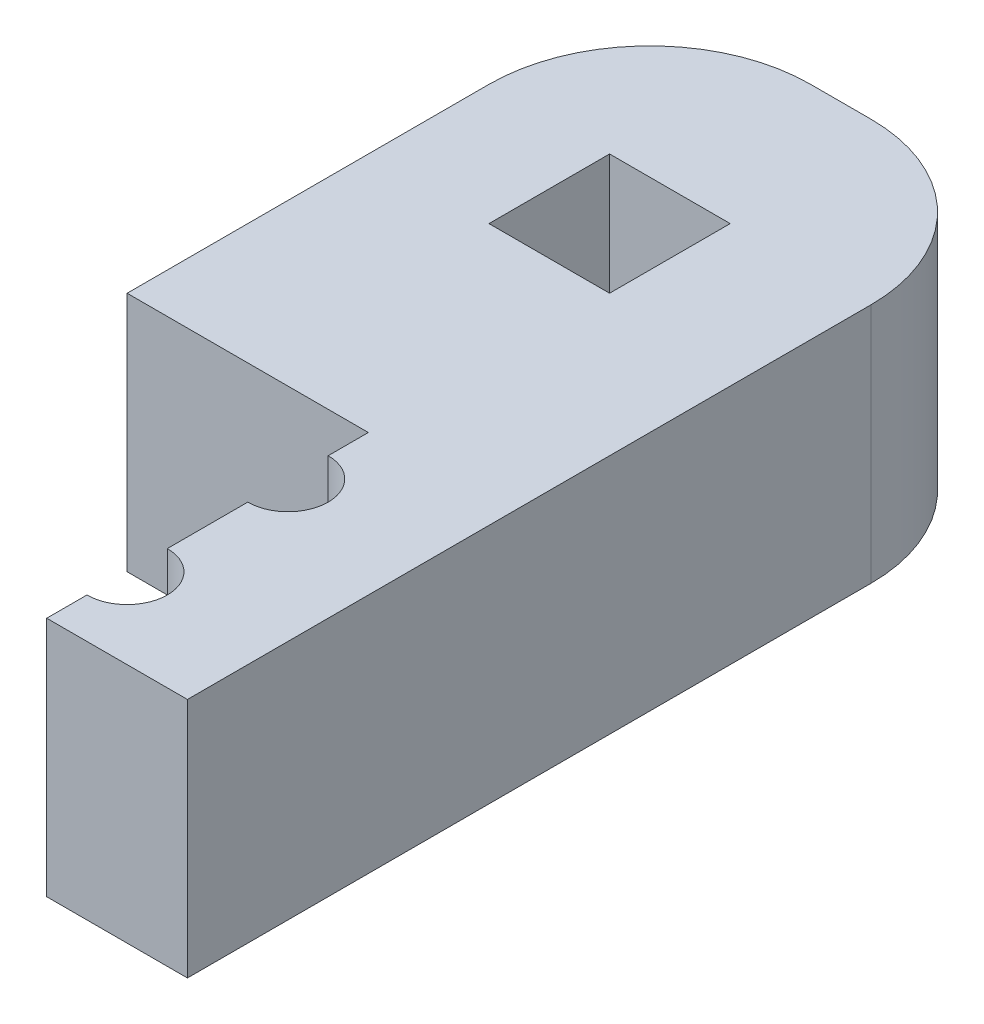
SolidWorks part; units mm, degrees
ref_plane "Front Plane" through (0, 0, 0) normal (0, 0, 1) x (1, 0, 0)
ref_plane "Top Plane" through (0, 0, 0) normal (0, 1, 0) x (1, 0, 0)
ref_plane "Right Plane" through (0, 0, 0) normal (1, 0, 0) x (0, 0, -1)
sketch "Sketch1" plane through (0, 0, 0) normal (0, 1, 0) x (1, 0, 0)
  line L3 (0, 13) -> (9.5, 13)
  line L4 (9.5, -8) -> (9.5, 13)
  line L5 (0, 0) -> (6, 0)
  line L6 (6, 0) -> (6, -8)
  line L7 (6, -8) -> (9.5, -8)
  line L8 (0, 0) -> (0, 13)
  dimension "D1" = 13
  dimension "D2" = 0
  dimension "D3" = 8
  dimension "D4" = 6
  dimension "D5" = 3.5
extrude "Boss-Extrude1" add sketch "Sketch1" along normal blind 6
sketch "Sketch2" plane through (0, 6, 0) normal (0, 1, 0) x (1, 0, 0)
  line L1 (3, 9) -> (6, 9)
  line L2 (3, 9) -> (3, 6)
  line L3 (3, 6) -> (6, 6)
  line L4 (6, 9) -> (6, 6)
  line L6 (9.5, 13) -> (0, 13) construction
  line L8 (0, 13) -> (0, 0) construction
  line L11 (0, 0) -> (6, 0) construction
  line L12 (6, 0) -> (6, -8) construction
  line L13 (6, -8) -> (9.5, -8) construction
  circle A0 centre (6, -2) radius 1
  circle A1 centre (6, -6) radius 1
  dimension "D3" = 2
  dimension "D6" = 2
  dimension "D7" = 2
  dimension "D1" = 3
  dimension "D2" = 3
  dimension "D4" = 3
  dimension "D5" = 4
  dimension "D8" = 2
extrude "Cut-Extrude1" cut sketch "Sketch2" against normal through all
fillet "Fillet1" radius 4 2 edges at (9.5, 3, -13) (0, 3, -13)
